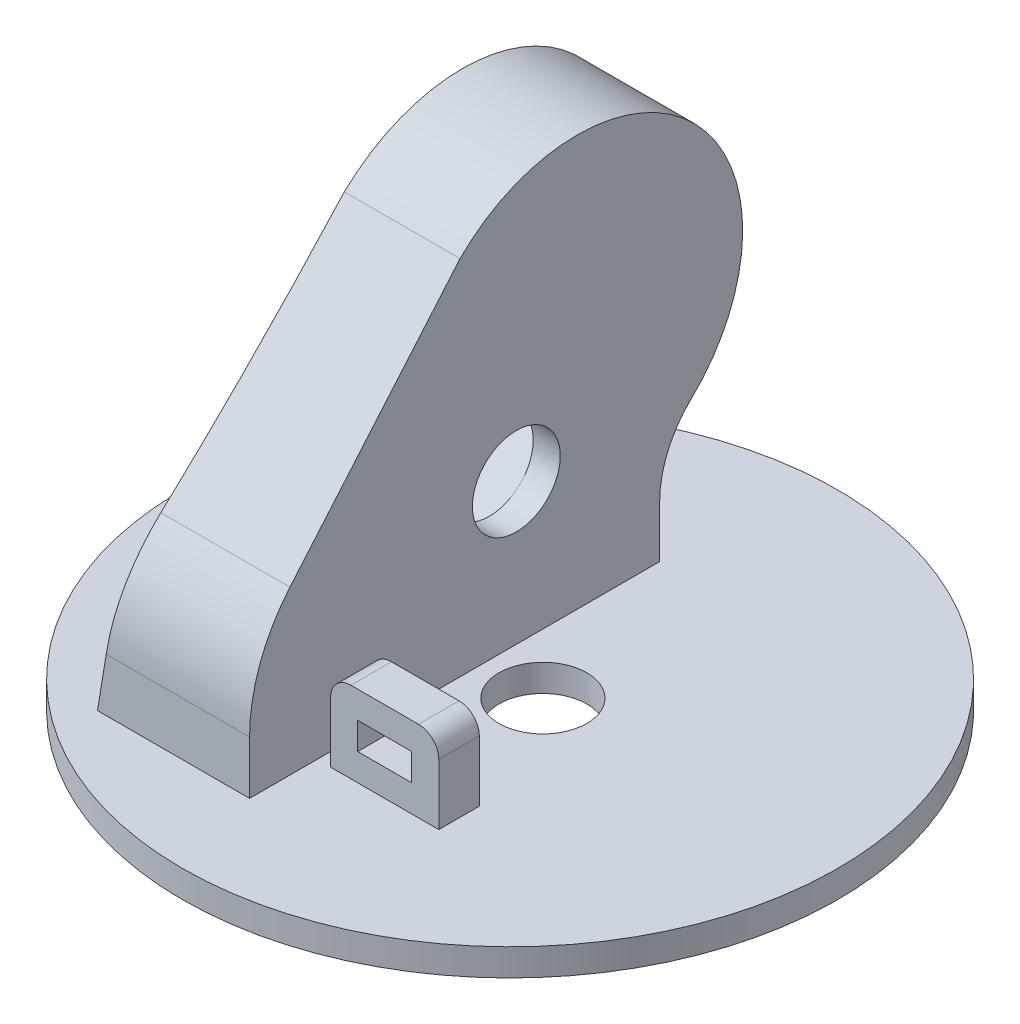
SolidWorks part; units mm, degrees
ref_plane "Front Plane" through (0, 0, 0) normal (0, 0, 1) x (1, 0, 0)
ref_plane "Top Plane" through (0, 0, 0) normal (0, 1, 0) x (1, 0, 0)
ref_plane "Right Plane" through (0, 0, 0) normal (1, 0, 0) x (0, 0, -1)
sketch "Sketch2" plane through (0, 0, 0) normal (0, 1, 0) x (1, 0, 0)
  circle A0 centre (0, 0) radius 48.5
  dimension "D1" = 97
extrude "Boss-Extrude1" add sketch "Sketch2" along normal blind 4
sketch "Sketch5" plane through (0, 0, 0) normal (0, -1, 0) x (1, 0, 0)
  circle A0 centre (4.855, 0) radius 6.5
  dimension "D1" = 13
extrude "Cut-Extrude3" cut sketch "Sketch5" against normal through all
ref_plane "Plane1" through (-4, 0, 0) normal (1, 0, 0) x (0, 0, -1)
sketch "Sketch7" plane through (-4, 0, 0) normal (1, 0, 0) x (0, 0, -1)
  line L0 (23.1299, 11.6445) -> (23.1299, 4)
  line L5 (48.5, 4) -> (-48.5, 4) construction
  line L6 (-27.2273, 29.5362) -> (-1.2843, 55.4793)
  line L7 (-43.5609, 4) -> (23.1299, 4)
  line L11 (-34.5496, 4) -> (-34.5496, 11.8586)
  arc A4 (28.7298, 24.692) -> (-1.2843, 55.4793) centre (13.9185, 40.2765) ccw
  arc A5 (28.7298, 24.692) -> (23.1299, 11.6445) centre (41.1299, 11.6445) ccw
  arc A6 (-27.2273, 29.5362) -> (-34.5496, 11.8586) centre (-9.5496, 11.8586) ccw
  dimension "D1" = 25
  dimension "D4" = 43
  dimension "D3" = 18
  dimension "D5" = 45
extrude "Boss-Extrude2" add sketch "Sketch7" against normal blind 14 contours A5 A4 L6 L7 L0 | A4 | A4 | A4 | L6 A6 L7 region at (-4, 29.3392, -2.7362)
ref_plane "Plane2" through (-6, 0, 0) normal (1, 0, 0) x (0, 0, -1)
sketch "Sketch17" plane through (-18, 0, 0) normal (-1, 0, 0) x (0, 0, 1)
  line L0 (29.3486, 31.6576) -> (3.4056, 57.6006)
  line L1 (-26.1299, 11.6445) -> (-26.1299, 1)
  line L2 (-26.1299, 1) -> (37.5496, 1)
  line L3 (37.5496, 1) -> (37.5496, 11.8586)
  line L4 (27.2273, 29.5362) -> (1.2843, 55.4793)
  line L5 (-23.1299, 11.6445) -> (-23.1299, 4)
  line L6 (-23.1299, 4) -> (34.5496, 4)
  line L7 (34.5496, 4) -> (34.5496, 11.8586)
  line L9 (-23.1299, 11.6445) -> (-23.1299, 4)
  line L10 (-23.1299, 4) -> (34.5496, 4)
  line L11 (34.5496, 4) -> (34.5496, 11.8586)
  line L12 (-26.1299, 4) -> (37.5496, 4)
  line L13 (48.5, 4) -> (-48.5, 4) construction
  line L14 (3.4056, 57.6006) -> (28.5745, 28.0776)
  line L15 (1.2843, 55.4793) -> (26.295, 26.1272)
  line L16 (31.5496, 11.8586) -> (31.5496, 4)
  line L18 (27.2273, 29.5362) -> (1.2843, 55.4793) construction
  arc A0 (3.4056, 57.6006) -> (-30.7965, 22.5174) centre (-13.9185, 40.2765) ccw
  arc A1 (-26.1299, 11.6445) -> (-30.7965, 22.5174) centre (-41.1299, 11.6445) ccw
  arc A2 (37.5496, 11.8586) -> (29.3486, 31.6576) centre (9.5496, 11.8586) ccw
  arc A3 (1.2843, 55.4793) -> (-28.7298, 24.692) centre (-13.9185, 40.2765) ccw
  arc A4 (-23.1299, 11.6445) -> (-28.7298, 24.692) centre (-41.1299, 11.6445) ccw
  arc A5 (34.5496, 11.8586) -> (27.2273, 29.5362) centre (9.5496, 11.8586) ccw
  arc A6 (1.2843, 55.4793) -> (-28.7298, 24.692) centre (-13.9185, 40.2765) ccw
  arc A7 (-23.1299, 11.6445) -> (-28.7298, 24.692) centre (-41.1299, 11.6445) ccw
  arc A8 (34.5496, 11.8586) -> (27.2273, 29.5362) centre (9.5496, 11.8586) ccw
  arc A9 (31.5496, 11.8586) -> (25.106, 27.4149) centre (9.5496, 11.8586) ccw
  line M16 (27.2273, 29.5362) -> (1.2843, 55.4793)
  arc M17 (1.2843, 55.4793) -> (-28.7298, 24.692) centre (-13.9185, 40.2765) ccw
  arc M18 (-28.7298, 24.692) -> (-23.1299, 11.6445) centre (-41.1299, 11.6445) cw
  line M19 (-23.1299, 11.6445) -> (-23.1299, 4)
  line M21 (34.5496, 4) -> (34.5496, 11.8586)
  arc M22 (34.5496, 11.8586) -> (27.2273, 29.5362) centre (9.5496, 11.8586) ccw
  dimension "D1" = 0
  dimension "D2" = 3
  dimension "D3" = 3
extrude "Boss-Extrude7" add sketch "Sketch17" along normal blind 9 and the other way up to surface (14 mm away) contours A9 L16 L12 L15 M21 M22 M16 | A1 L1 L12 L14 A0 M19 M18 M17 M16 M22 region at (-18, 42.2523, 15.3017) region at (-18, 20.289, 32.4332) other way up to face at (-4, 22.5305, 1.4471)
sketch "Sketch25" plane through (-18, 0, 0) normal (-1, 0, 0) x (0, 0, 1)
  line L0 (-23.1299, 11.6445) -> (-23.1299, 4)
  line L1 (48.5, 4) -> (-48.5, 4) construction
  line L2 (-23.1299, 11.6445) -> (-23.1299, 4) construction
  line L3 (1.2843, 55.4793) -> (26.295, 26.1272) construction
  line L4 (31.5496, 4) -> (-23.1299, 4) construction
  line L5 (31.5496, 11.8586) -> (31.5496, 4) construction
  line L6 (31.5496, 4) -> (-23.1299, 4)
  line L7 (31.5496, 11.8586) -> (31.5496, 4)
  line L8 (1.2843, 55.4793) -> (26.295, 26.1272)
  arc A0 (-23.1299, 11.6445) -> (-28.7298, 24.692) centre (-41.1299, 11.6445) ccw construction
  arc A1 (1.2843, 55.4793) -> (-28.7298, 24.692) centre (-13.9185, 40.2765) ccw construction
  arc A2 (-23.1299, 11.6445) -> (-28.7298, 24.692) centre (-41.1299, 11.6445) ccw
  arc A3 (31.5496, 11.8586) -> (26.295, 26.1272) centre (9.5496, 11.8586) ccw construction
  arc A4 (31.5496, 11.8586) -> (26.295, 26.1272) centre (9.5496, 11.8586) ccw
  spline S0 degree 3 poles (-28.7298, 24.692) (-21.9549, 18.2532) (-19.0941, 12.798) (-15.1299, 4) knots 0 0 0 0 1 1 1 1
  spline S1 degree 2 poles (11.7516, 43.195) (26.5513, 25.8264) (25.5496, 4) knots 0 0 0 1 1 1
  dimension "D2" = 8
  dimension "D1" = 6
extrude "Boss-Extrude10" add sketch "Sketch25" along normal up to surface (9 mm away) contours S0 L6 L0 A2 | A4 S1 A2 S0 L8 region at (-18, 9.918, -20.706) region at (-18, 17.2593, 26.6261) up to face at (-27, 22.2911, 0.3951)
sketch "Sketch26" plane through (0, 0, 0) normal (0, 0, 1) x (1, 0, 0)
  line L0 (-4, 64.7765) -> (-27, 64.7765) construction
  line L1 (-27, 4) -> (-4, 4) construction
  line L2 (-27, 4) -> (-27, 11.8586) construction
  line L3 (-26, 64.7765) -> (-27, 64.7765)
  line L4 (-27, 64.7765) -> (-27, 4)
  line L5 (-27, 4) -> (-23, 4)
  spline S0 degree 2 poles (-26, 64.7765) (-24.7724, 34.3751) (-23, 4) knots 0 0 0 1 1 1
  dimension "D1" = 1
  dimension "D2" = 4
  dimension "D3" = 2
extrude "Cut-Extrude15" [suppressed] cut sketch "Sketch26" against normal through all both and the other way through all contours L4 L5 S0 L3
sketch "Sketch27" plane through (0, 4, 0) normal (0, 1, 0) x (1, 0, 0)
  line L1 (-2, -18.5496) -> (14, -18.5496)
  line L2 (-2, -18.5496) -> (-2, -24.5496)
  line L3 (-2, -24.5496) -> (14, -24.5496)
  line L4 (14, -18.5496) -> (14, -24.5496)
  line L5 (-27, -34.5496) -> (-4, -34.5496) construction
  line L6 (-4, -34.5496) -> (-4, 26.1299) construction
  dimension "D1" = 10
  dimension "D2" = 6
  dimension "D3" = 16
  dimension "D4" = 2
extrude "Boss-Extrude11" add sketch "Sketch27" along normal blind 12
fillet "Fillet6" radius 3 2 edges at (14, 16, 21.5496) (-2, 16, 21.5496)
sketch "Sketch28" plane through (0, 0, 24.5496) normal (0, 0, 1) x (1, 0, 0)
  line L8 (10, 12) -> (2, 12)
  line L9 (2, 12) -> (2, 8)
  line L10 (2, 8) -> (10, 8)
  line L11 (10, 8) -> (10, 12)
  line L12 (10, 12) -> (2, 12)
  line L13 (2, 12) -> (2, 8)
  line L14 (2, 8) -> (10, 8)
  line L15 (10, 8) -> (10, 12)
  dimension "D1" = 4
extrude "Cut-Extrude16" cut sketch "Sketch28" against normal up to next
sketch "Sketch29" plane through (0, 0, 0) normal (0, 0, 1) x (1, 0, 0)
  line L0 (-4, 64.7765) -> (-27, 64.7765) construction
  line L1 (-27, 4) -> (-4, 4) construction
  line L2 (-21, 64.7765) -> (-27, 64.7765)
  line L3 (-27, 64.7765) -> (-27, 4)
  line L4 (-27, 4) -> (-26.5, 4)
  line L5 (48.5, 4) -> (-48.5, 4) construction
  spline S0 degree 2 poles (-21, 64.7765) (-21.2205, 34.1409) (-26.5, 4) knots 0 0 0 1 1 1
  dimension "D1" = 6
  dimension "D2" = 4
  dimension "D3" = 0.5
  dimension "D4" = 25
extrude "Cut-Extrude17" cut sketch "Sketch29" against normal through all both and the other way through all
sketch "Sketch31" plane through (-18, 0, 0) normal (-1, 0, 0) x (0, 0, 1)
  line L0 (-5.4155, 34.0546) -> (11.7496, 18.7458)
  line L1 (11.7496, 18.7458) -> (3.0968, 9.0438)
  line L2 (3.0968, 9.0438) -> (-14.0683, 24.3526)
  line L3 (-14.0683, 24.3526) -> (-5.4155, 34.0546)
  circle A0 centre (-4.9225, 24.9054) radius 6.5
  dimension "D1" = 6.5
extrude "Cut-Extrude18" cut sketch "Sketch31" against normal through all contours A0
extrude "Cut-Extrude19" cut sketch "Sketch31<3>" against normal blind 10 contours L0 L1 L2 L3
sketch "Sketch31<3>" plane through (-18, 0, 0) normal (-1, 0, 0) x (0, 0, 1) same geometry as "Sketch31"
sketch "Sketch32" plane through (-18, 0, 0) normal (-1, 0, 0) x (0, 0, 1)
  line L2 (3.1671, 26.4002) -> (-6.5457, 14.6527) construction
  line L3 (-5.4155, 34.0546) -> (11.7496, 18.7458) construction
  circle A0 centre (-11.5845, 30.655) radius 0.9205
  arc A4 (-9.2489, 29.7564) -> (-10.2349, 28.6509) centre (-4.9225, 24.9054) ccw construction
  circle A5 centre (10.1184, 12.7111) radius 0.9205
  dimension "D1" = 2.3
extrude "Cut-Extrude20" cut sketch "Sketch32" against normal blind 4 contours A0
extrude "Cut-Extrude21" cut sketch "Sketch32<3>" against normal blind 4
sketch "Sketch32<3>" plane through (-18, 0, 0) normal (-1, 0, 0) x (0, 0, 1) same geometry as "Sketch32"
